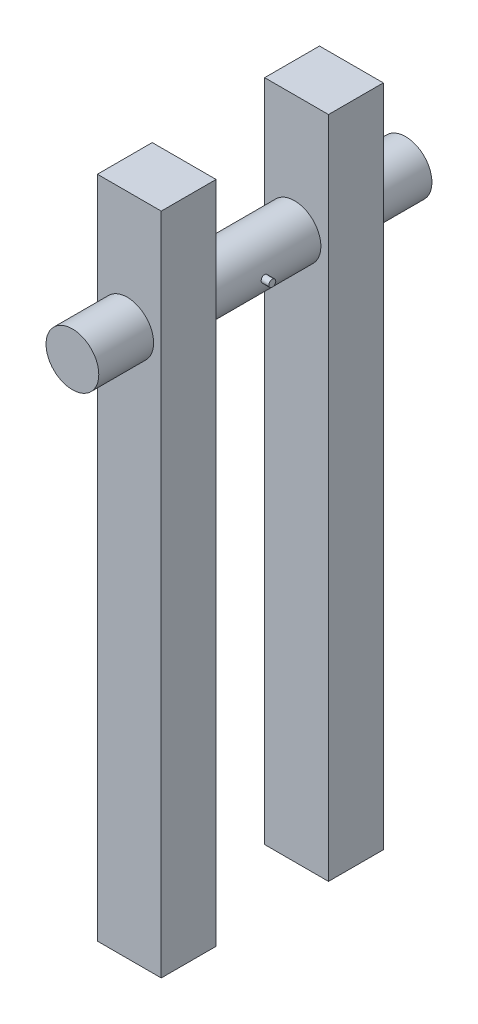
SolidWorks part; units mm, degrees
ref_plane "Front Plane" through (0, 0, 0) normal (0, 0, 1) x (1, 0, 0)
ref_plane "Top Plane" through (0, 0, 0) normal (0, 1, 0) x (1, 0, 0)
ref_plane "Right Plane" through (0, 0, 0) normal (1, 0, 0) x (0, 0, -1)
sketch "Sketch1" plane through (0, 0, 0) normal (1, 0, 0) x (0, 0, -1)
  line L0 (-32.1217, 47.1792) -> (-24.2217, 47.1792)
  line L1 (-8.0217, 47.1792) -> (-0.1217, 47.1792)
  line L2 (-8.0217, 47.1792) -> (-8.0217, -48.5208)
  line L3 (-8.0217, -48.5208) -> (-0.1217, -48.5208)
  line L4 (-0.1217, 47.1792) -> (-0.1217, -48.5208)
  line L5 (-32.1217, 47.1792) -> (-32.1217, -48.5208)
  line L6 (-32.1217, -48.5208) -> (-24.2217, -48.5208)
  line L7 (-24.2217, 47.1792) -> (-24.2217, -48.5208)
  dimension "D1" = 7.9
  dimension "D2" = 95.7
  dimension "D3" = 16.2
extrude "Boss-Extrude1" add sketch "Sketch1" along normal blind 9.2 contours L7 L6 L5 L0
extrude "Boss-Extrude2" add sketch "Sketch1<3>" along normal blind 9.2
sketch "Sketch1<3>" plane through (0, 0, 0) normal (1, 0, 0) x (0, 0, -1) same geometry as "Sketch1"
sketch "Sketch2" plane through (0, 0, 8.0217) normal (0, 0, 1) x (1, 0, 0)
  line L0 (9.2, 47.1792) -> (0, 47.1792) construction
  line L1 (9.2, 47.1792) -> (9.2, -48.5208) construction
  circle A0 centre (4.3, 30.1792) radius 3.8
  dimension "D1" = 7.6
  dimension "D2" = 17
  dimension "D3" = 4.9
extrude "Boss-Extrude3" add sketch "Sketch2" along normal blind 32 and the other way blind 16
sketch3d "3DSketch1"
  point P0 (8.0916, 29.9273, 15.2057)
sketch "Sketch4" plane through (9.2, 0, 0) normal (1, 0, 0) x (0, 0, -1)
  line L0 (-8.0217, 47.1792) -> (-8.0217, -48.5208) construction
  line L1 (-24.2217, 47.1792) -> (-8.0217, 47.1792)
  circle A0 centre (-16.1217, 30.1792) radius 0.5
  point P4 (-16.1217, 30.1792)
  dimension "D2" = 1
  dimension "D3" = 17
  dimension "D1" = 8.1
extrude "Boss-Extrude4" add sketch "Sketch4" against normal blind 6 and the other way blind 0.0001 contours A0
